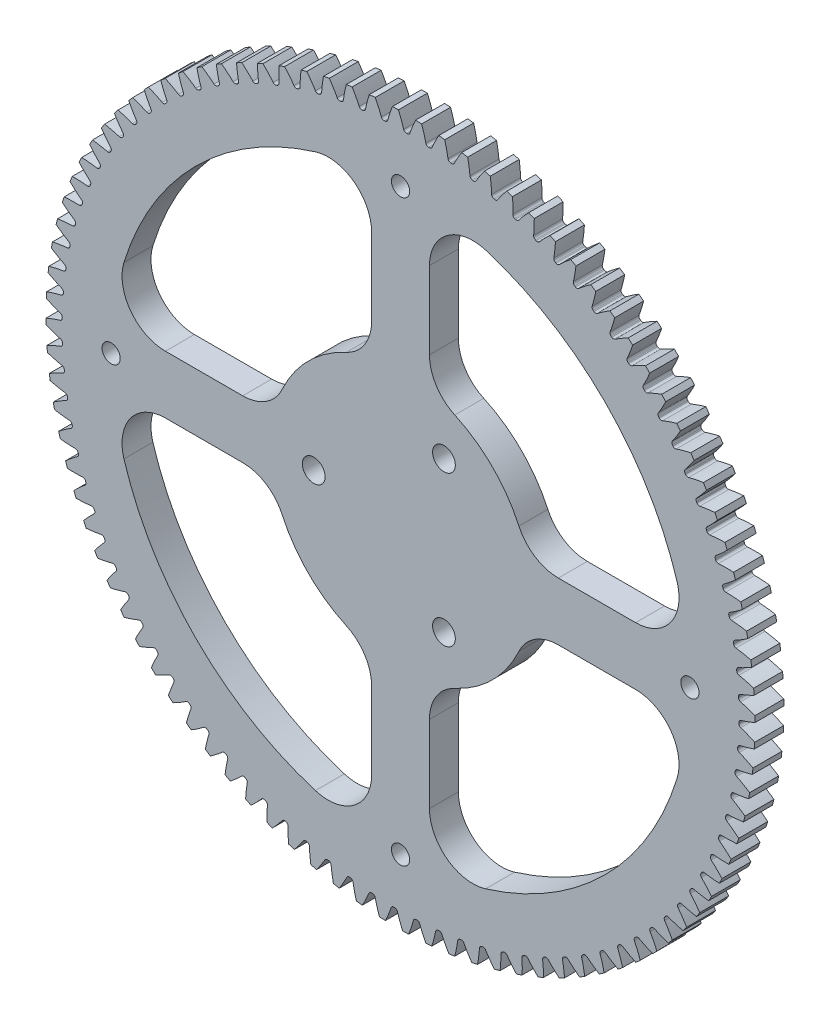
SolidWorks part; units mm, degrees
ref_plane "Front" through (0, 0, 0) normal (0, 0, 1) x (1, 0, 0)
ref_plane "Top" through (0, 0, 0) normal (0, 1, 0) x (1, 0, 0)
ref_plane "Right" through (0, 0, 0) normal (1, 0, 0) x (0, 0, -1)
sketch "Sketch3" plane through (0, 0, 0) normal (0, 0, 1) x (1, 0, 0)
  circle A0 centre (0, 0) radius 77.7875
  dimension "od" = 155.575
extrude "gearBody" add sketch "Sketch3" along normal blind 6.35
sketch "Sketch2" plane through (0, 0, 0) normal (0, 0, 1) x (1, 0, 0)
  line L0 (0, 0) -> (66.154, 27.4019) construction
  line L1 (89.9379, -14.1817) -> (0, 0) construction
  line L2 (0, 0) -> (36.3143, 0) construction
  line L3 (76.1998, -0.172) -> (76.1546, -2.6294) construction
  line L5 (76.1772, -1.4007) -> (0, 0) construction
  line L7 (0, 0) -> (71.6046, 0) construction
  arc A0 (71.5902, -1.4371) -> (71.5946, -1.1957) centre (0, 0) ccw construction
  arc A1 (77.7861, 0.4588) -> (77.7167, -3.3181) centre (0, 0) ccw construction
  arc A2 (76.1998, -0.172) -> (76.1546, -2.6294) centre (0, 0) ccw construction
  arc A3 (74.2296, -1.47) -> (74.2335, -1.2598) centre (0, 0) ccw
  arc A4 (89.9379, -14.1817) -> (74.6441, -2.0632) centre (65.1019, -29.8153) ccw
  arc A5 (89.9379, -14.1817) -> (90.3984, 10.8657) centre (0, 0) ccw
  arc A6 (90.3984, 10.8657) -> (74.6695, -0.6823) centre (66.154, 27.4019) cw
  arc A7 (74.2335, -1.2598) -> (74.6695, -0.6823) centre (74.8478, -1.2702) cw
  arc A8 (74.6441, -2.0632) -> (74.2296, -1.47) centre (74.8439, -1.4822) cw
  point P6 (90.3984, 10.8657)
  point P22 (89.9379, -14.1817)
  dimension "baseDia" = 143.2092
  dimension "od" = 155.575
  dimension "pd" = 152.4
  dimension "rd" = 148.4884
  dimension "rFillet" = 0.6144
  dimension "pointX" = 90.3984
  dimension "pointY" = 10.8657
  dimension "CTT" = 2.4574
  dimension "flankCenterAngle" = 22.5
extrude "toothCut" cut sketch "Sketch2" along normal through all
pattern_circular "CirPattern1" count 96 over 360 about axis through (0, 0, 6.35) along (0, 0, -1) of "toothCut"
sketch "hub1Dia" plane through (0, 0, 0) normal (0, 0, -1) x (-1, 0, 0)
  circle A0 centre (0, 0) radius 12.7
  dimension "hub1Dia" = 25.4
sketch "hub2Dia" plane through (0, 0, 6.35) normal (0, 0, 1) x (1, 0, 0)
  circle A0 centre (0, 0) radius 12.7
  dimension "hub2dia" = 25.4
sketch "boreDia" plane through (0, 0, 0) normal (0, 0, 1) x (1, 0, 0)
  circle A0 centre (0, 0) radius 7.9375
  dimension "boreDia" = 15.875
sketch "Sketch4" plane through (0, 0, 0) normal (0, 0, -1) x (-1, 0, 0)
  circle A0 centre (19.05, 0) radius 2.5
  circle A1 centre (-9.525, -16.4978) radius 2.5
  circle A2 centre (-9.525, 16.4978) radius 2.5
  point P10 (0, 0)
  dimension "D2" = 5
  dimension "D1" = 19.05
  dimension "D3" = 3
extrude "Cut-Extrude1" cut sketch "Sketch4" against normal through all
sketch "Sketch5" plane through (0, 0, 0) normal (0, 0, -1) x (-1, 0, 0)
  circle A0 centre (63.5, 0) radius 2
  circle A1 centre (0, -63.5) radius 2
  circle A2 centre (-63.5, 0) radius 2
  circle A3 centre (0, 63.5) radius 2
  point P12 (0, 0)
  dimension "D1" = 4
  dimension "D2" = 63.5
  dimension "D3" = 4
extrude "Cut-Extrude2" cut sketch "Sketch5" against normal through all
sketch "Sketch6" plane through (0, 0, 0) normal (0, 0, -1) x (-1, 0, 0)
  line L0 (6.35, 63.1817) -> (6.35, 27.8605)
  line L1 (27.8605, 6.35) -> (63.1817, 6.35)
  arc A0 (27.8605, 6.35) -> (6.35, 27.8605) centre (0, 0) ccw
  arc A1 (63.1817, 6.35) -> (6.35, 63.1817) centre (0, 0) ccw
  dimension "D1" = 127
  dimension "D2" = 57.15
  dimension "D3" = 6.35
  dimension "D4" = 6.35
extrude "Cut-Extrude3" cut sketch "Sketch6" against normal through all
sketch "Sketch7" plane through (0, 0, 0) normal (0, 1, 0) x (1, 0, 0)
  line L0 (0, 0) -> (0, 31.0261)
pattern_circular "CirPattern2" count 4 over 360 about axis through (0, 0, 0) along (0, 0, -1) of "Cut-Extrude3"
fillet "Fillet1" radius 9.525 16 edges at (-27.8605, -6.35, 3.175) (-6.35, -27.8605, 3.175) (6.35, -27.8605, 3.175) (27.8605, -6.35, 3.175) (27.8605, 6.35, 3.175) (6.35, 27.8605, 3.175) (-27.8605, 6.35, 3.175) (-6.35, 27.8605, 3.175) (-6.35, 63.1817, 3.175) (6.35, 63.1817, 3.175) (63.1817, 6.35, 3.175) (63.1817, -6.35, 3.175) (6.35, -63.1817, 3.175) (-6.35, -63.1817, 3.175) (-63.1817, -6.35, 3.175) (-63.1817, 6.35, 3.175)
equation "\"D2@Sketch4\"=5mm"
equation "\"D1@Sketch5\"=4mm"
